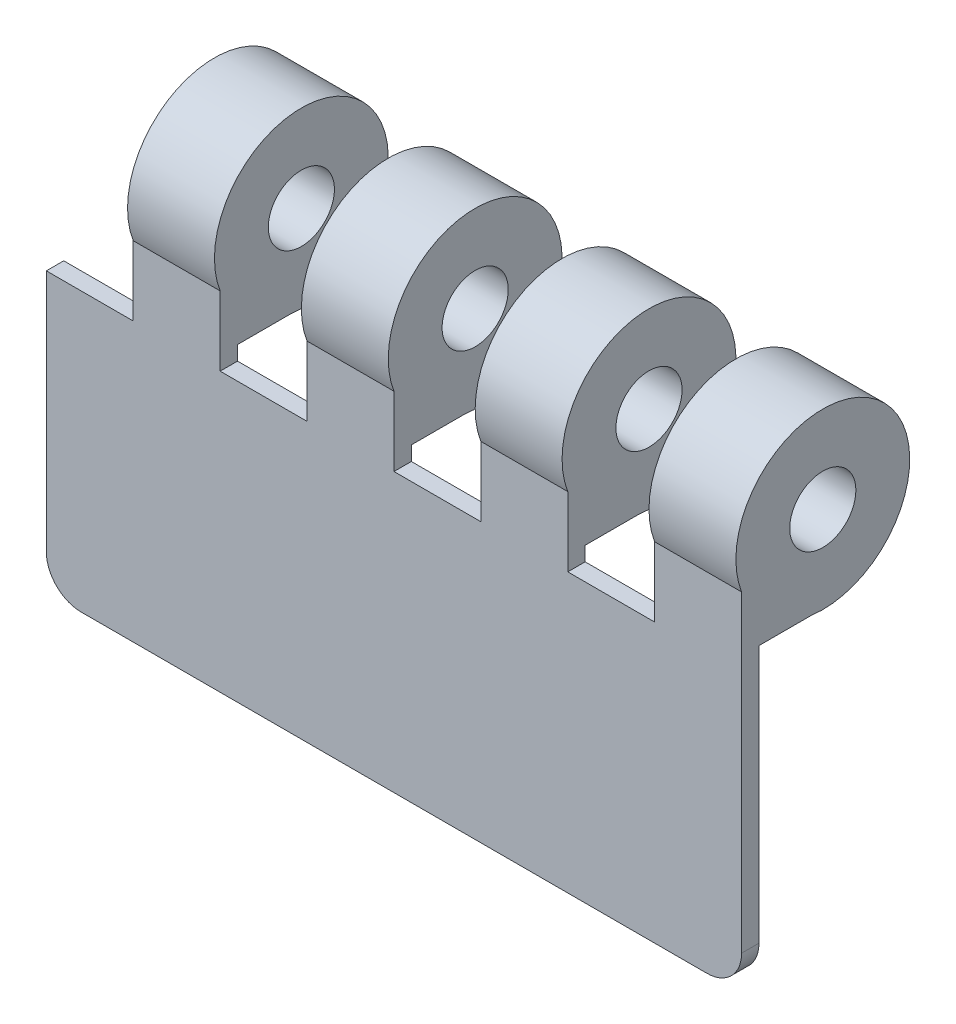
SolidWorks part; units mm, degrees
ref_plane "Front Plane" through (0, 0, 0) normal (0, 0, 1) x (1, 0, 0)
ref_plane "Top Plane" through (0, 0, 0) normal (0, 1, 0) x (1, 0, 0)
ref_plane "Right Plane" through (0, 0, 0) normal (1, 0, 0) x (0, 0, -1)
sketch "Sketch1" plane through (0, 0, 0) normal (0, 0, 1) x (1, 0, 0)
  line L1 (-25.4, -12.7) -> (25.4, -12.7)
  line L2 (-25.4, -12.7) -> (-25.4, 12.7)
  line L3 (-25.4, 12.7) -> (25.4, 12.7)
  line L4 (25.4, -12.7) -> (25.4, 12.7)
  line L5 (-25.4, -12.7) -> (25.4, 12.7) construction
  line L6 (-25.4, 12.7) -> (25.4, -12.7) construction
  point P0 (0, 0)
extrude "Boss-Extrude1" add sketch "Sketch1" along normal blind 5.08
sketch "Sketch2" plane through (25.4, 0, 0) normal (1, 0, 0) x (0, 0, -1)
  circle A0 centre (0.8539, 14.9609) radius 6.35
  circle A2 centre (0.8539, 14.9609) radius 2.4168
extrude "Boss-Extrude5" add sketch "Sketch2" against normal blind 6.35 contours A0
sketch "Sketch6" plane through (0, 0, 0) normal (0, 0, -1) x (-1, 0, 0)
  line L0 (-25.4, 14.9609) -> (32.4196, 14.9609) construction
  line L1 (-25.4, 21.3109) -> (-25.4, 8.6109) construction
pattern_linear "LPattern2" count 4 spacing 12.7 along (-1, 0, 0) of "Boss-Extrude5"
sketch "Sketch7" plane through (0, 12.7, 0) normal (0, 1, 0) x (1, 0, 0)
  line L4 (19.05, 0) -> (12.7, 0)
  line L5 (12.7, 0) -> (12.7, -5.08)
  line L6 (12.7, -5.08) -> (19.05, -5.08)
  line L8 (19.05, 0) -> (12.7, 0)
  line L9 (12.7, 0) -> (12.7, -5.08)
  line L12 (6.35, 0) -> (0, 0)
  line L13 (0, 0) -> (0, -5.08)
  line L14 (0, -5.08) -> (6.35, -5.08)
  line L16 (6.35, 0) -> (0, 0)
  line L17 (0, 0) -> (0, -5.08)
  line L20 (-6.35, 0) -> (-12.7, 0)
  line L21 (-12.7, 0) -> (-12.7, -5.08)
  line L22 (-12.7, -5.08) -> (-6.35, -5.08)
  line L24 (-6.35, 0) -> (-12.7, 0)
  line L25 (-12.7, 0) -> (-12.7, -5.08)
  line L28 (-19.05, -5.08) -> (-19.05, 0)
  line L29 (-19.05, 0) -> (-25.4, 0)
  line L30 (-25.4, 0) -> (-25.4, -5.08)
  line L33 (-19.05, 0) -> (-25.4, 0)
  line L34 (-25.4, 0) -> (-25.4, -5.08)
  line L36 (12.7, -5.08) -> (19.05, -5.08)
  line L38 (0, -5.08) -> (6.35, -5.08)
  line L40 (-12.7, -5.08) -> (-6.35, -5.08)
  line L42 (-19.05, -5.08) -> (-19.05, 0)
  line L44 (19.05, -5.08) -> (19.05, 0)
  line L45 (19.05, -5.08) -> (19.05, 0)
  line L46 (6.35, -5.08) -> (6.35, 0)
  line L47 (6.35, -5.08) -> (6.35, 0)
  line L48 (-6.35, -5.08) -> (-6.35, 0)
  line L49 (-6.35, -5.08) -> (-6.35, 0)
  line L50 (-25.4, -5.08) -> (-19.05, -5.08)
  line L51 (-25.4, -5.08) -> (-19.05, -5.08)
  dimension "D1" = 0
  dimension "D2" = 0
  dimension "D3" = 0
  dimension "D4" = 0
extrude "Cut-Extrude2" cut sketch "Sketch7" against normal blind 5.08
sketch "Sketch8" plane through (0, 0, 0) normal (0, 0, -1) x (-1, 0, 0)
  line L18 (-19.05, 7.62) -> (-19.05, 8.6686)
  line L19 (-19.05, 8.6686) -> (-25.4, 8.6686)
  line L20 (-25.4, 8.6686) -> (-25.4, -12.7)
  line L21 (-25.4, -12.7) -> (25.4, -12.7)
  line L22 (25.4, -12.7) -> (25.4, 7.62)
  line L23 (25.4, 7.62) -> (19.05, 7.62)
  line L24 (19.05, 7.62) -> (19.05, 8.6686)
  line L25 (19.05, 8.6686) -> (12.7, 8.6686)
  line L26 (12.7, 8.6686) -> (12.7, 7.62)
  line L27 (12.7, 7.62) -> (6.35, 7.62)
  line L28 (6.35, 7.62) -> (6.35, 8.6686)
  line L29 (6.35, 8.6686) -> (0, 8.6686)
  line L30 (0, 8.6686) -> (0, 7.62)
  line L31 (0, 7.62) -> (-6.35, 7.62)
  line L32 (-6.35, 7.62) -> (-6.35, 8.6686)
  line L33 (-6.35, 8.6686) -> (-12.7, 8.6686)
  line L34 (-12.7, 8.6686) -> (-12.7, 7.62)
  line L35 (-12.7, 7.62) -> (-19.05, 7.62)
  line L36 (-19.05, 7.62) -> (-19.05, 8.6686)
  line L37 (-19.05, 8.6686) -> (-25.4, 8.6686)
  line L38 (-25.4, 8.6686) -> (-25.4, -12.7)
  line L39 (-25.4, -12.7) -> (25.4, -12.7)
  line L40 (25.4, -12.7) -> (25.4, 7.62)
  line L41 (25.4, 7.62) -> (19.05, 7.62)
  line L42 (19.05, 7.62) -> (19.05, 8.6686)
  line L43 (19.05, 8.6686) -> (12.7, 8.6686)
  line L44 (12.7, 8.6686) -> (12.7, 7.62)
  line L45 (12.7, 7.62) -> (6.35, 7.62)
  line L46 (6.35, 7.62) -> (6.35, 8.6686)
  line L47 (6.35, 8.6686) -> (0, 8.6686)
  line L48 (0, 8.6686) -> (0, 7.62)
  line L49 (0, 7.62) -> (-6.35, 7.62)
  line L50 (-6.35, 7.62) -> (-6.35, 8.6686)
  line L51 (-6.35, 8.6686) -> (-12.7, 8.6686)
  line L52 (-12.7, 8.6686) -> (-12.7, 7.62)
  line L53 (-12.7, 7.62) -> (-19.05, 7.62)
  dimension "D1" = 0
extrude "Cut-Extrude3" cut sketch "Sketch8" against normal blind 3.81
fillet "Fillet1" radius 2.54 2 edges at (-25.4, -12.7, 4.445) (25.4, -12.7, 4.445)
extrude "Cut-Extrude6" cut sketch "Sketch2<5>" against normal blind 76.2 contours A2
sketch "Sketch2<5>" plane through (25.4, 0, 0) normal (1, 0, 0) x (0, 0, -1) same geometry as "Sketch2"
